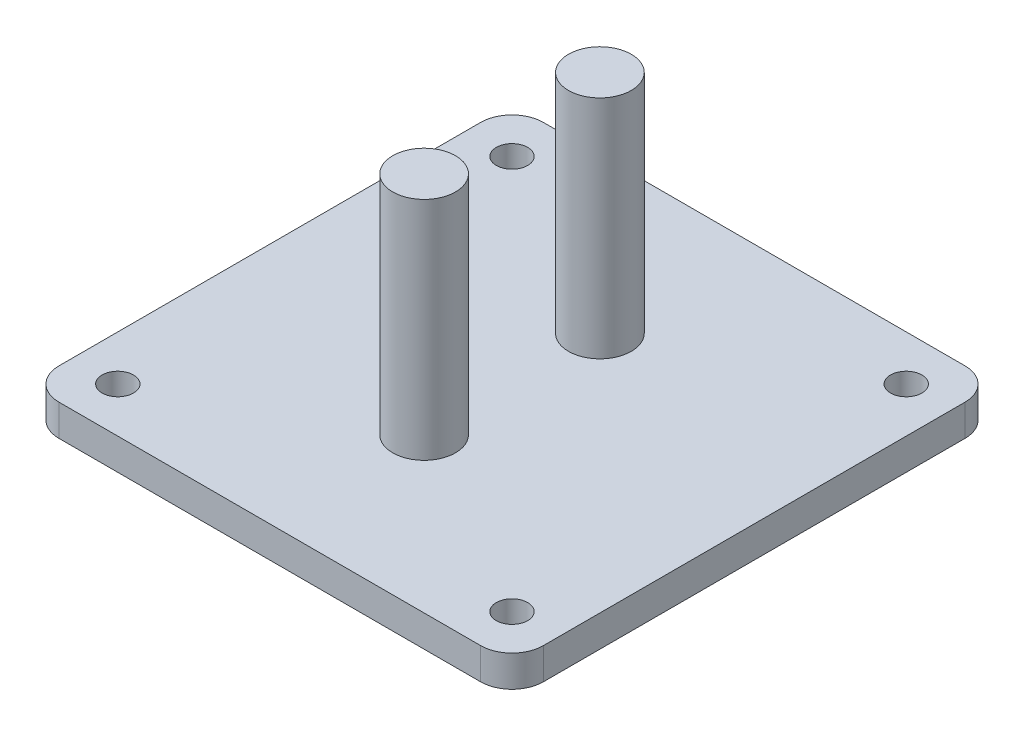
SolidWorks part; units mm, degrees
ref_plane "Płaszczyzna przednia" through (0, 0, 0) normal (0, 0, 1) x (1, 0, 0)
ref_plane "Płaszczyzna górna" through (0, 0, 0) normal (0, 1, 0) x (1, 0, 0)
ref_plane "Płaszczyzna prawa" through (0, 0, 0) normal (1, 0, 0) x (0, 0, -1)
sketch "Szkic1" plane through (0, 0, 0) normal (0, 1, 0) x (1, 0, 0)
  line L1 (16.795, -19.295) -> (-16.795, -19.295)
  line L2 (19.295, -16.795) -> (19.295, 16.795)
  line L3 (16.795, 19.295) -> (-16.795, 19.295)
  line L4 (-19.295, -16.795) -> (-19.295, 16.795)
  line L5 (19.295, -19.295) -> (-19.295, 19.295) construction
  line L6 (19.295, 19.295) -> (-19.295, -19.295) construction
  arc A0 (-16.795, -19.295) -> (-19.295, -16.795) centre (-16.795, -16.795) cw
  arc A1 (16.795, -19.295) -> (19.295, -16.795) centre (16.795, -16.795) ccw
  arc A2 (19.295, 16.795) -> (16.795, 19.295) centre (16.795, 16.795) ccw
  arc A3 (-16.795, 19.295) -> (-19.295, 16.795) centre (-16.795, 16.795) ccw
  circle A4 centre (0, 7) radius 2.5
  circle A5 centre (0, -7) radius 2.5
  point P0 (0, 0)
  point P25 (0, 0)
  dimension "D3" = 2.5
  dimension "D4" = 7
  dimension "D5" = 5
  dimension "D1" = 38.59
  dimension "D2" = 38.59
  dimension "D6" = 2
extrude "Dodanie-wyciągnięcie1" add sketch "Szkic1" along normal blind 2.5 contours L3 A3 L4 A0 L1 A1 L2 A2
extrude "Dodanie-wyciągnięcie2" add sketch "Szkic1<4>" along normal blind 20.5 contours A4 | A5
sketch "Szkic1<4>" plane through (0, 0, 0) normal (0, 1, 0) x (1, 0, 0) same geometry as "Szkic1"
sketch "Szkic2" plane through (0, 2.5, 0) normal (0, 1, 0) x (1, 0, 0)
  circle A0 centre (-15.7, 15.7) radius 1.25
  circle A2 centre (15.7, 15.7) radius 1.25
  circle A3 centre (15.7, -15.7) radius 1.25
  circle A4 centre (-15.7, -15.7) radius 1.25
  point P12 (0, 0)
  dimension "D1" = 15.7
  dimension "D3" = 2.5
  dimension "D2" = 15.7
  dimension "D4" = 4
extrude "Wytnij-wyciągnięcie1" cut sketch "Szkic2" against normal blind 2.5
sketch "Szkic3" plane through (0, 0, 0) normal (0, -1, 0) x (1, 0, 0)
  circle A0 centre (-12.3, 0) radius 2.5
  circle A1 centre (12.3, 0) radius 2.5
  point P8 (0, 0)
  dimension "D1" = 5
  dimension "D2" = 12.3
  dimension "D3" = 2
extrude "Wytnij-wyciągnięcie2" cut sketch "Szkic3" against normal blind 1
